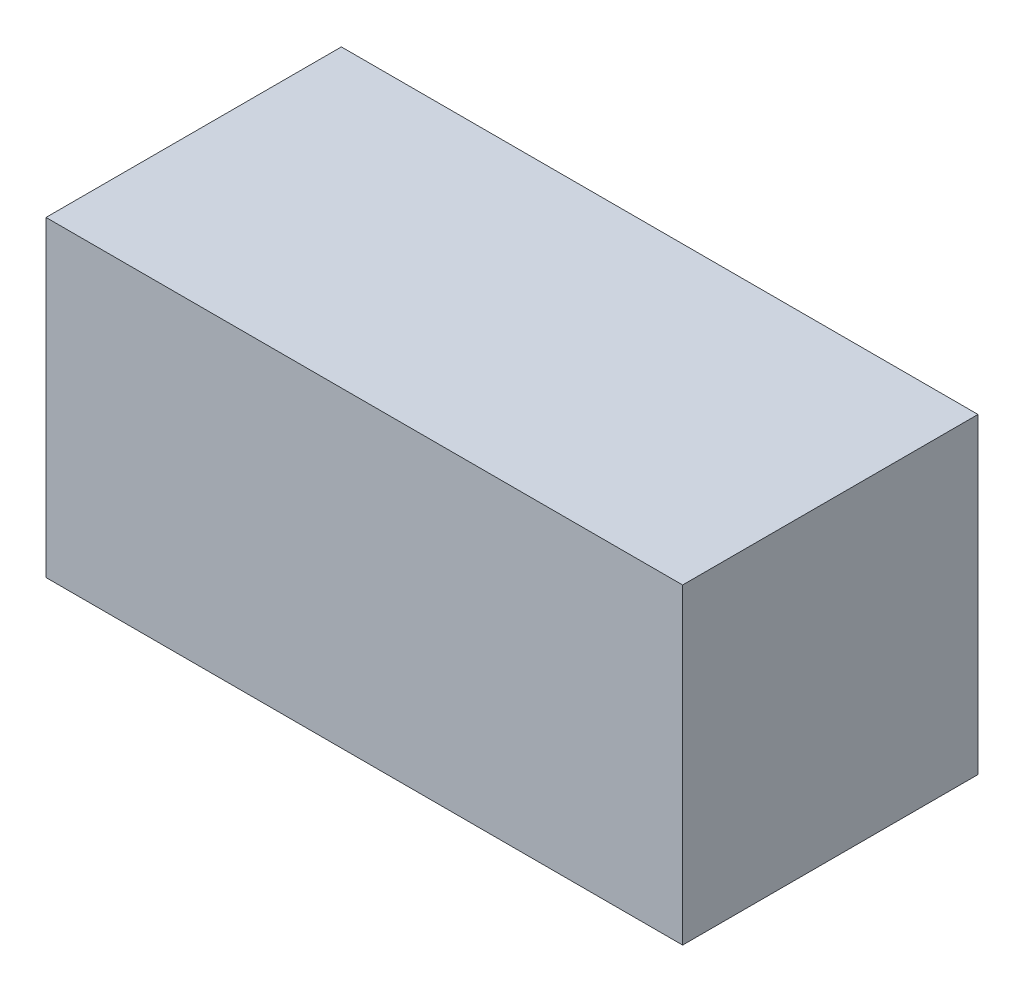
SolidWorks part; units mm, degrees
material "Handl."
ref_plane "Płaszczyzna przednia" through (0, 0, 0) normal (0, 0, 1) x (1, 0, 0)
ref_plane "Płaszczyzna górna" through (0, 0, 0) normal (0, 1, 0) x (1, 0, 0)
ref_plane "Płaszczyzna prawa" through (0, 0, 0) normal (1, 0, 0) x (0, 0, -1)
sketch "Szkic1" plane through (0, 0, 0) normal (0, 1, 0) x (1, 0, 0)
  line L1 (173.5, -80.5) -> (-173.5, -80.5)
  line L2 (173.5, -80.5) -> (173.5, 80.5)
  line L3 (173.5, 80.5) -> (-173.5, 80.5)
  line L4 (-173.5, -80.5) -> (-173.5, 80.5)
  line L5 (173.5, -80.5) -> (-173.5, 80.5) construction
  line L6 (173.5, 80.5) -> (-173.5, -80.5) construction
  point P0 (0, 0)
  dimension "D1" = 347
  dimension "D2" = 161
extrude "Dodanie-wyciągnięcie1" add sketch "Szkic1" along normal mid plane 170
